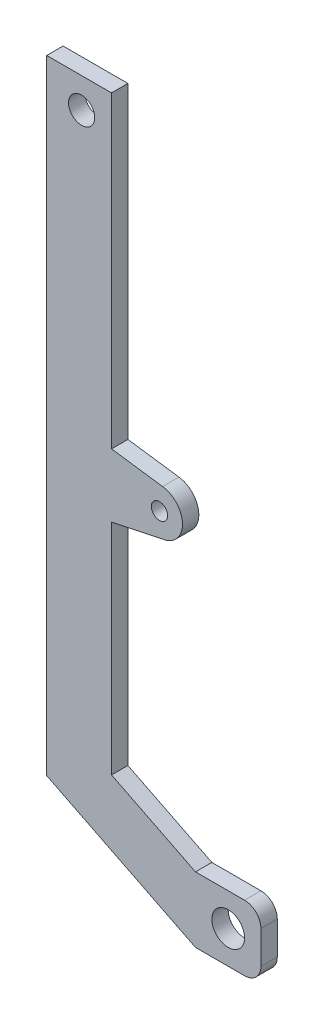
SolidWorks part; units mm, degrees
ref_plane "Front Plane" through (0, 0, 0) normal (0, 0, 1) x (1, 0, 0)
ref_plane "Top Plane" through (0, 0, 0) normal (0, 1, 0) x (1, 0, 0)
ref_plane "Right Plane" through (0, 0, 0) normal (1, 0, 0) x (0, 0, -1)
sketch "Sketch1" plane through (0, 0, 0) normal (0, 0, 1) x (1, 0, 0)
  line L0 (-10, 10) -> (10, 10)
  line L1 (10, 10) -> (10, -10)
  line L2 (10, -10) -> (-10, -10)
  line L12 (0, 0) -> (67.8578, 0) construction
  line L13 (-85.9774, 80) -> (-110, 80) construction
  line L14 (-100, 172.9697) -> (-100, 80) construction
  line L17 (0, 0) -> (0, 249.807) construction
  line L18 (-92.1407, 77.1927) -> (-83.9804, 80.9048) construction
  line L19 (-83.0728, 52.7744) -> (-72.0556, 62.9902) construction
  line L20 (0, 0) -> (-39.6944, 40.4963) construction
  line L24 (-79.9152, 86.788) -> (-79.467, 70.983) construction
  line L33 (-79.467, 70.983) -> (-69.6254, 58.6079) construction
  line L45 (-69.6254, 58.6079) -> (-79.9152, 86.788) construction
  line L51 (-11, 115) -> (-11, 85) construction
  line L56 (-11, 115) -> (-21, 100) construction
  line L57 (82.8895, 212.3203) -> (5.5915, 72.231) construction
  line L58 (-30, 20) -> (30, 20) construction
  line L59 (-30, 20) -> (-30, 180) construction
  line L60 (-30, 180) -> (30, 180) construction
  line L61 (30, 20) -> (30, 180) construction
  line L62 (-30, 20) -> (30, 180) construction
  line L63 (-30, 180) -> (30, 20) construction
  line L68 (82.8895, 212.3203) -> (135.423, 183.3336) construction
  line L69 (5.5915, 72.231) -> (58.125, 43.2443) construction
  line L70 (135.423, 183.3336) -> (58.125, 43.2443) construction
  line L71 (109.1562, 197.827) -> (31.8583, 57.7376) construction
  line L72 (-98.7689, 157.7553) -> (42.1544, 203.3398) construction
  line L77 (-21, 100) -> (-11, 85) construction
  line L78 (-11, 100) -> (-21, 100) construction
  line L79 (-19.5557, 93.1223) -> (-35.6529, 89.7418)
  line L80 (-35.6529, 89.7418) -> (-35.6529, 22.8264)
  line L81 (-10, 10) -> (-35.6529, 22.8264)
  line L82 (-20.0379, 106.9616) -> (-35.6529, 109.1196)
  line L83 (-35.6529, 109.1196) -> (-35.6529, 203.3398)
  line L84 (0, 0) -> (-55.461, 264.1001) construction
  line L85 (-10, -10) -> (-55.461, 12.7305)
  line L87 (-35.6529, 203.3398) -> (-55.461, 203.3398)
  line L88 (-55.461, 203.3398) -> (-55.461, 12.7305)
  circle A0 centre (0, 0) radius 5
  arc A3 (-93.1578, 80) -> (41.9046, 115.4226) centre (0, 0) cw construction
  arc A10 (-10, 10) -> (-83.0728, 52.7744) centre (-10, 93.8033) ccw construction
  circle A13 centre (-79.9152, 86.788) radius 11 construction
  circle A14 centre (-69.6254, 58.6079) radius 11 construction
  arc A15 (-64.4376, 76.4709) -> (0, 100) centre (0, 0) cw construction
  circle A16 centre (0, 100) radius 70 construction
  circle A17 centre (-79.467, 70.983) radius 5 construction
  arc A18 (-83.9804, 80.9048) -> (-72.0556, 62.9902) centre (-79.467, 70.983) cw construction
  arc A20 (-100, 156.8374) -> (0, 186.0053) centre (0, 0) cw construction
  circle A21 centre (40, 210) radius 7 construction
  circle A24 centre (-11, 115) radius 11 construction
  circle A25 centre (-11, 85) radius 11 construction
  circle A26 centre (-21, 100) radius 2.5
  arc A27 (-19.5557, 93.1223) -> (-20.0379, 106.9616) centre (-21, 100) ccw
  circle A29 centre (-44.7901, 194.1725) radius 4
  point P63 (-63.5329, 77.2241)
  dimension "D1" = 10
  dimension "D7" = 60
  dimension "D27" = 22
  dimension "D22" = 100
  dimension "D23" = 140
  dimension "D16" = 14
  dimension "D12" = 22
  dimension "D18" = 5
  dimension "D2" = 10
  dimension "D3" = 10
  dimension "D4" = 10
  dimension "D5" = 93.1578
  dimension "D6" = 100
  dimension "D8" = 20
  dimension "D9" = 80
  dimension "D10" = 40
  dimension "D11" = 80
  dimension "D14" = 30
  dimension "D15" = 210
  dimension "D17" = 10
  dimension "D25" = 30
extrude "Boss-Extrude1" add sketch "Sketch1" along normal blind 5
fillet "Fillet3" radius 5 2 edges at (10, -10, 2.5) (10, 10, 2.5)
